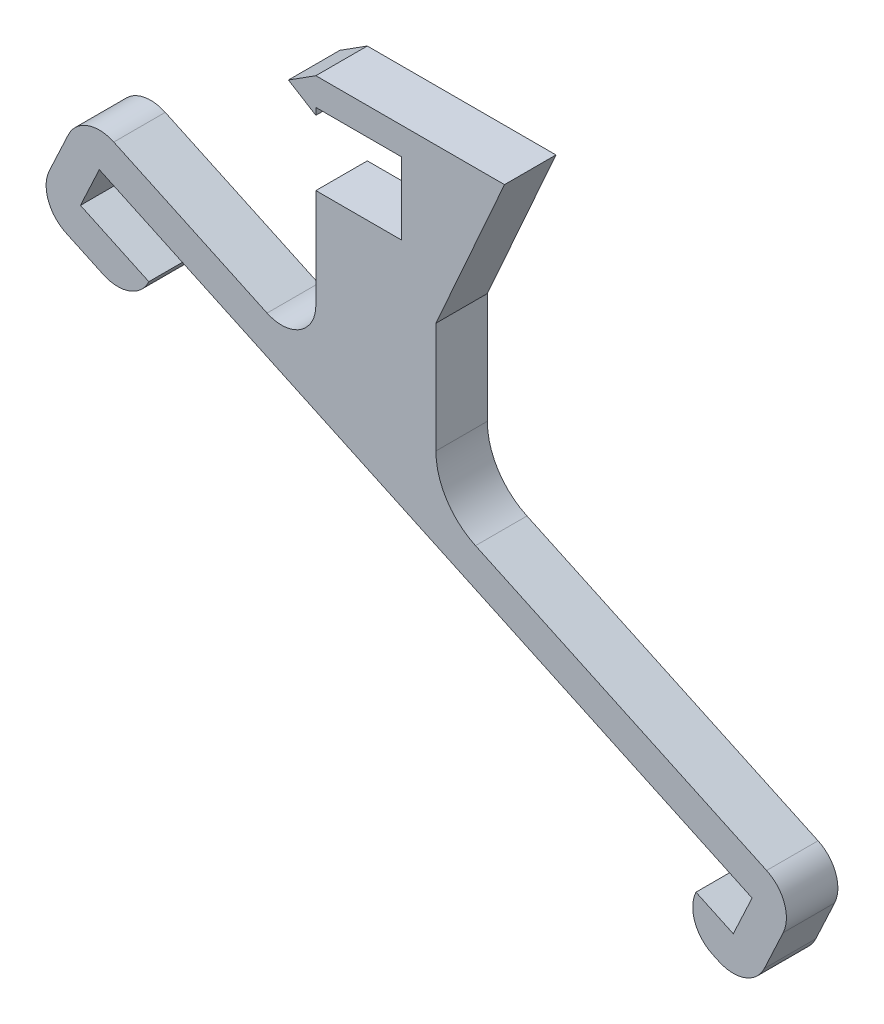
SolidWorks part; units mm, degrees
ref_plane "Front Plane" through (0, 0, 0) normal (0, 0, 1) x (1, 0, 0)
ref_plane "Top Plane" through (0, 0, 0) normal (0, 1, 0) x (1, 0, 0)
ref_plane "Right Plane" through (0, 0, 0) normal (1, 0, 0) x (0, 0, -1)
sketch "Sketch1" plane through (0, 0, 0) normal (0, 0, 1) x (1, 0, 0)
  line L0 (0, 0) -> (-25, 0)
  line L1 (-25, 0) -> (-25, -2)
  line L2 (-25, -2) -> (-33, 2.914)
  line L3 (-33, 2.914) -> (-25, 8)
  line L4 (-25, 8) -> (10, 8)
  line L5 (10, -37) -> (10, -82)
  line L6 (10, -82) -> (115.4777, -131.1851)
  line L7 (115.4777, -131.1851) -> (101.5313, -161.0932)
  line L8 (101.5313, -161.0932) -> (81.5925, -151.7956)
  line L9 (81.5925, -151.7956) -> (85.8187, -142.7325)
  line L10 (85.8187, -142.7325) -> (96.6944, -147.804)
  line L11 (96.6944, -147.804) -> (102.1884, -136.022)
  line L12 (102.1884, -136.022) -> (-88.1362, -47.2721)
  line L13 (-88.1362, -47.2721) -> (-93.6302, -59.0541)
  line L14 (-93.6302, -59.0541) -> (-73.6915, -68.3517)
  line L15 (-73.6915, -68.3517) -> (-77.9176, -77.4148)
  line L16 (-77.9176, -77.4148) -> (-106.9195, -63.891)
  line L17 (-106.9195, -63.891) -> (-92.9731, -33.9829)
  line L18 (-92.9731, -33.9829) -> (-25, -65.6792)
  line L19 (-25, -65.6792) -> (-25, -21)
  line L20 (-25, -21) -> (0, -21)
  line L21 (0, -21) -> (0, 0)
  line L22 (-25, -65.6792) -> (10, -82) construction
  line L23 (-73.6915, -68.3517) -> (85.8187, -142.7325) construction
  line L24 (81.5925, -151.7956) -> (-77.9176, -77.4148) construction
  line L25 (-25, 8) -> (-25, 0) construction
  line L27 (10, 8) -> (30, 8)
  line L28 (30, 8) -> (10, -37)
  point P25 (-33, 2.914)
  point P26 (0, 0)
  dimension "D1" = 25
  dimension "D2" = 21
  dimension "D3" = 2
  dimension "D4" = 8
  dimension "D5" = 8
  dimension "D6" = 10
  dimension "D7" = 90
  dimension "D8" = 210
  dimension "D9" = 10
  dimension "D10" = 10
  dimension "D11" = 10
  dimension "D12" = 10
  dimension "D13" = 13
  dimension "D14" = 12
  dimension "D15" = 22
  dimension "D16" = 65
  dimension "D17" = 75
  dimension "D18" = 20
extrude "Boss-Extrude1" add sketch "Sketch1" along normal blind 15
fillet "Fillet1" radius 10 7 edges at (115.4777, -131.1851, 7.5) (101.5313, -161.0932, 7.5) (81.5925, -151.7956, 7.5) (-77.9176, -77.4148, 7.5) (-106.9195, -63.891, 7.5) (-92.9731, -33.9829, 7.5) (-25, -65.6792, 7.5)
fillet "Fillet2" radius 20 1 edges at (10, -82, 7.5)
